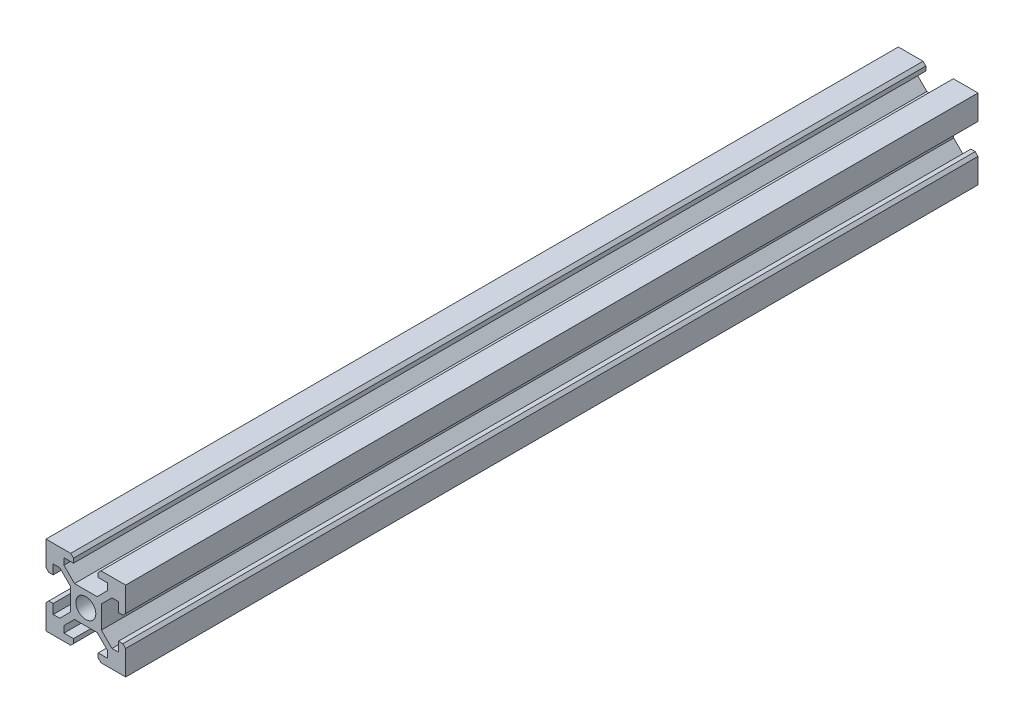
SolidWorks part; units mm, degrees
material "1060 Alloy"
ref_plane "Front Plane" through (0, 0, 0) normal (0, 0, 1) x (1, 0, 0)
ref_plane "Top Plane" through (0, 0, 0) normal (0, 1, 0) x (1, 0, 0)
ref_plane "Right Plane" through (0, 0, 0) normal (1, 0, 0) x (0, 0, -1)
sketch "Sketch1" plane through (0, 0, 0) normal (0, 0, 1) x (1, 0, 0)
  line L0 (3.9, -2.8393) -> (6.5607, -5.5)
  line L1 (-10, 10) -> (10, 10) construction
  line L2 (-10, 10) -> (-10, -10) construction
  line L3 (-10, -10) -> (10, -10) construction
  line L4 (10, 10) -> (10, -10) construction
  line L5 (-10, 10) -> (10, -10) construction
  line L6 (-10, -10) -> (10, 10) construction
  line L7 (-3.9, -3.9) -> (3.9, -3.9) construction
  line L8 (-3.9, -3.9) -> (-3.9, 3.9) construction
  line L9 (-3.9, 3.9) -> (3.9, 3.9) construction
  line L10 (3.9, -3.9) -> (3.9, 3.9) construction
  line L11 (-3.9, -3.9) -> (3.9, 3.9) construction
  line L12 (-3.9, 3.9) -> (3.9, -3.9) construction
  line L13 (-10, 10) -> (-5.5, 10) construction
  line L14 (-10, 10) -> (-10, 5.5) construction
  line L15 (-10, 5.5) -> (-5.5, 5.5) construction
  line L16 (-5.5, 10) -> (-5.5, 5.5) construction
  line L17 (10, 10) -> (5.5, 10) construction
  line L18 (10, 10) -> (10, 5.5) construction
  line L19 (10, 5.5) -> (5.5, 5.5) construction
  line L20 (5.5, 10) -> (5.5, 5.5) construction
  line L21 (-10, -10) -> (-5.5, -10) construction
  line L22 (-10, -10) -> (-10, -5.5) construction
  line L23 (-10, -5.5) -> (-5.5, -5.5) construction
  line L24 (-5.5, -10) -> (-5.5, -5.5) construction
  line L25 (10, -10) -> (5.5, -10) construction
  line L26 (10, -10) -> (10, -5.5) construction
  line L27 (10, -5.5) -> (5.5, -5.5) construction
  line L28 (5.5, -10) -> (5.5, -5.5) construction
  line L29 (2.8393, -3.9) -> (5.5, -6.5607)
  line L30 (-5.5, 6.5607) -> (-2.8393, 3.9)
  line L31 (-6.5607, 5.5) -> (-3.9, 2.8393)
  line L32 (5.5, 6.5607) -> (2.8393, 3.9)
  line L33 (6.5607, 5.5) -> (3.9, 2.8393)
  line L34 (-6.5607, -5.5) -> (-3.9, -2.8393)
  line L35 (-5.5, -6.5607) -> (-2.8393, -3.9)
  line L36 (-2.8393, 3.9) -> (2.8393, 3.9)
  line L37 (-3.9, 2.8393) -> (-3.9, -2.8393)
  line L38 (-2.8393, -3.9) -> (2.8393, -3.9)
  line L39 (3.9, -2.8393) -> (3.9, 2.8393)
  line L40 (5.5, 6.5607) -> (5.5, 8.2007)
  line L41 (5.5, 8.2007) -> (3.1, 8.2007)
  line L42 (3.1, 8.2007) -> (3.1, 9.3)
  line L43 (3.1, 9.3) -> (3.8, 10)
  line L44 (3.8, 10) -> (10, 10)
  line L45 (10, 10) -> (10, 3.8)
  line L46 (10, 3.8) -> (9.3, 3.1)
  line L47 (9.3, 3.1) -> (8.2007, 3.1)
  line L48 (8.2007, 3.1) -> (8.2007, 5.5)
  line L49 (8.2007, 5.5) -> (6.5607, 5.5)
  line L50 (3.1, -8.2007) -> (5.5, -8.2007)
  line L51 (3.1, -9.3) -> (3.1, -8.2007)
  line L52 (3.8, -10) -> (3.1, -9.3)
  line L53 (10, -10) -> (3.8, -10)
  line L54 (10, -3.8) -> (10, -10)
  line L55 (9.3, -3.1) -> (10, -3.8)
  line L56 (8.2007, -3.1) -> (9.3, -3.1)
  line L57 (8.2007, -5.5) -> (8.2007, -3.1)
  line L58 (6.5607, -5.5) -> (8.2007, -5.5)
  line L59 (5.5, -8.2007) -> (5.5, -6.5607)
  line L60 (-8.2007, -3.1) -> (-8.2007, -5.5)
  line L61 (-9.3, -3.1) -> (-8.2007, -3.1)
  line L62 (-10, -3.8) -> (-9.3, -3.1)
  line L63 (-10, -10) -> (-10, -3.8)
  line L64 (-3.8, -10) -> (-10, -10)
  line L65 (-3.1, -9.3) -> (-3.8, -10)
  line L66 (-3.1, -8.2007) -> (-3.1, -9.3)
  line L67 (-5.5, -8.2007) -> (-3.1, -8.2007)
  line L68 (-5.5, -6.5607) -> (-5.5, -8.2007)
  line L69 (-8.2007, -5.5) -> (-6.5607, -5.5)
  line L70 (-3.1, 8.2007) -> (-5.5, 8.2007)
  line L71 (-3.1, 9.3) -> (-3.1, 8.2007)
  line L72 (-3.8, 10) -> (-3.1, 9.3)
  line L73 (-10, 10) -> (-3.8, 10)
  line L74 (-10, 3.8) -> (-10, 10)
  line L75 (-9.3, 3.1) -> (-10, 3.8)
  line L76 (-8.2007, 3.1) -> (-9.3, 3.1)
  line L77 (-8.2007, 5.5) -> (-8.2007, 3.1)
  line L78 (-6.5607, 5.5) -> (-8.2007, 5.5)
  line L79 (-5.5, 8.2007) -> (-5.5, 6.5607)
  circle A0 centre (0, 0) radius 2.5
  point P83 (0, 0)
  dimension "D1" = 5
  dimension "D2" = 20
  dimension "D3" = 7.8
  dimension "D4" = 4.5
  dimension "D5" = 1.5
  dimension "D6" = 0.75
  dimension "D7" = 1.5
  dimension "D8" = 0.75
  dimension "D9" = 1.5
  dimension "D10" = 0.75
  dimension "D11" = 1.5
  dimension "D12" = 0.75
  dimension "D13" = 1.64
  dimension "D14" = 45
  dimension "D15" = 3.1
  dimension "D16" = 6.2
  dimension "D17" = 6.2
  dimension "D18" = 3.1
  dimension "D19" = 4
extrude "Boss-Extrude1" add sketch "Sketch1" along normal mid plane 214 contours L79 L70 L71 L72 L73 L74 L75 L76 L77 L78 L31 L37 L34 L69 L60 L61 L62 L63 L64 L65 L66 L67 L68 L35 L38 L29 L59 L50 L51 L52 L53 L54 L55 L56 L57 L58 L0 L39 L33 L49 L48 L47 L46 L45 L44 L43 L42 L41 L40 L32 L36 region at (5.0303, -4.3697, 0)
